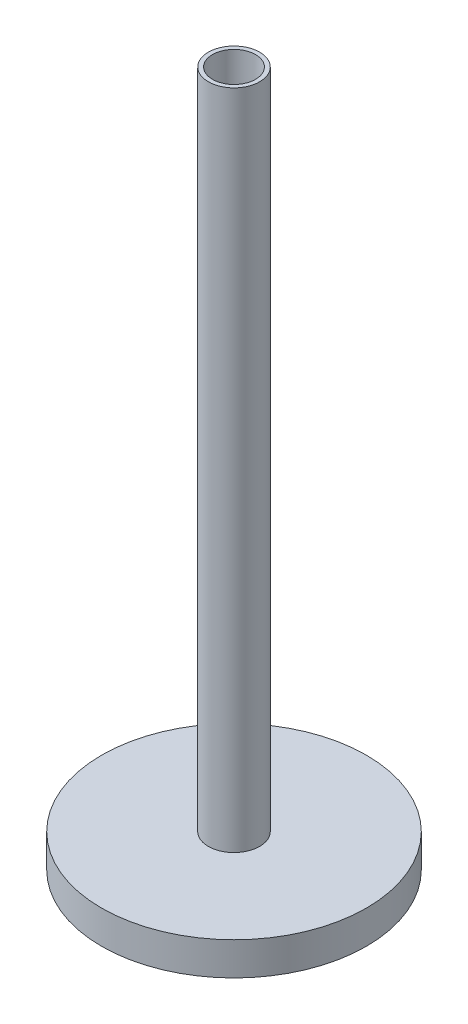
SolidWorks part; units mm, degrees
ref_plane "Front Plane" through (0, 0, 0) normal (0, 0, 1) x (1, 0, 0)
ref_plane "Top Plane" through (0, 0, 0) normal (0, 1, 0) x (1, 0, 0)
ref_plane "Right Plane" through (0, 0, 0) normal (1, 0, 0) x (0, 0, -1)
sketch "Sketch1" plane through (0, 0, 0) normal (0, 1, 0) x (1, 0, 0)
  circle A0 centre (0, 0) radius 7.75
  circle A1 centre (0, 0) radius 6.5
  dimension "D1" = 15.5
  dimension "D2" = 13
extrude "Boss-Extrude1" add sketch "Sketch1" along normal blind 200
sketch "Sketch2" plane through (0, 0, 0) normal (0, -1, 0) x (-1, 0, 0)
  circle A0 centre (0, 0) radius 40.0005
  circle A1 centre (0, 0) radius 7.75
  dimension "D1" = 15.5
extrude "Boss-Extrude2" add sketch "Sketch2" along normal blind 10
extrude "Boss-Extrude3" add sketch "Sketch1<2>" against normal blind 20.4764
sketch "Sketch1<2>" plane through (0, 0, 0) normal (0, 1, 0) x (1, 0, 0) same geometry as "Sketch1"
